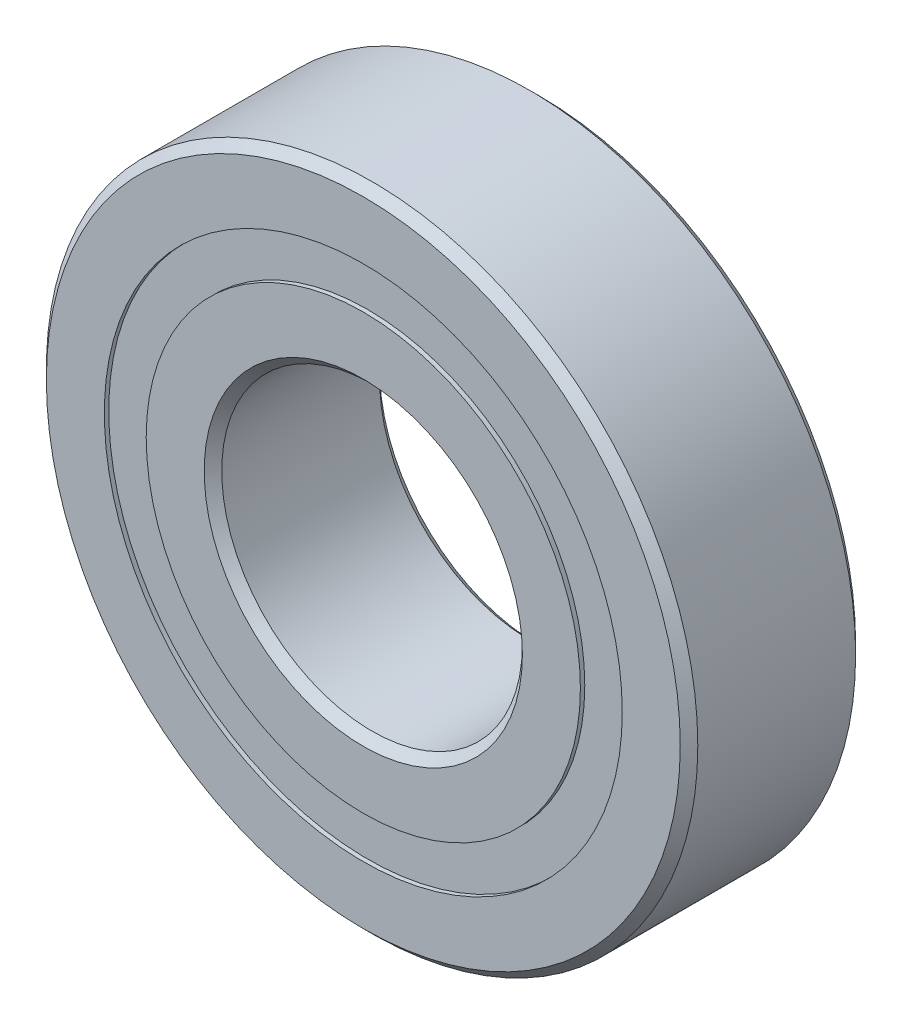
SolidWorks part; units mm, degrees
ref_plane "Front Plane" through (0, 0, 0) normal (0, 0, 1) x (1, 0, 0)
ref_plane "Top Plane" through (0, 0, 0) normal (0, 1, 0) x (1, 0, 0)
ref_plane "Right Plane" through (0, 0, 0) normal (1, 0, 0) x (0, 0, -1)
sketch "Sketch1" plane through (0, 0, 0) normal (1, 0, 0) x (0, 0, -1)
  line L0 (-5.5562, 0) -> (5.5562, 0) construction
  line L1 (0, 20.6375) -> (0, -20.6375) construction
  line L2 (5.0006, 20.6375) -> (-5.0006, 20.6375)
  line L3 (-5.0006, 20.6375) -> (-5.5563, 20.0819)
  line L4 (-5.5563, 20.0819) -> (-5.5563, 16.4071)
  line L5 (-5.5563, 16.4071) -> (-2.4694, 16.4071)
  line L6 (5.5563, 16.4071) -> (2.4694, 16.4071)
  line L7 (5.5563, 20.0819) -> (5.5563, 16.4071)
  line L8 (5.0006, 20.6375) -> (5.5563, 20.0819)
  line L9 (0, 20.6375) -> (0, 15.0813) construction
  line L10 (0, 15.0813) -> (0, 9.525) construction
  arc A0 (-2.4694, 16.4071) -> (2.4694, 16.4071) centre (0, 15.0813) cw
  point P14 (0, 9.525)
  dimension "Width" = 11.1125
  dimension "OD" = 41.275
  dimension "D1" = 45
  dimension "D2" = 0.5556
  dimension "Shaft Dia" = 19.05
  dimension "D3" = 4.9389
  dimension "D4" = 1.3258
revolve "Revolve1" add sketch "Sketch1" angle 360 about L0
sketch "Sketch3" plane through (0, 0, 0) normal (1, 0, 0) x (0, 0, -1)
  line L0 (-5.5563, 13.7554) -> (-2.4694, 13.7554)
  line L1 (0, 20.6375) -> (0, -20.6375) construction
  line L2 (-5.5563, 20.0819) -> (-5.5563, 16.4071) construction
  line L3 (-5.5563, 13.7554) -> (-5.5563, 10.0806)
  line L4 (-5.0006, 20.6375) -> (-5.5563, 20.0819) construction
  line L5 (-5.5563, 10.0806) -> (-5.0006, 9.525)
  line L6 (-5.0006, 9.525) -> (5.0006, 9.525)
  line L7 (5.0006, 20.6375) -> (5.0006, -20.6375) construction
  line L8 (5.0006, 9.525) -> (5.5563, 10.0806)
  line L9 (5.5563, -20.0819) -> (5.5563, 20.0819) construction
  line L10 (5.5563, 10.0806) -> (5.5563, 13.7554)
  line L11 (5.5563, 13.7554) -> (2.4694, 13.7554)
  line L13 (5.0006, 20.6375) -> (5.5563, 20.0819) construction
  arc A0 (2.4694, 16.4071) -> (-2.4694, 16.4071) centre (0, 15.0813) ccw construction
  arc A1 (2.4694, 13.7554) -> (-2.4694, 13.7554) centre (0, 15.0812) cw
revolve "Revolve3" add sketch "Sketch3" angle 360 about L0
sketch "Sketch4" plane through (0, 0, 0) normal (1, 0, 0) x (0, 0, -1)
  line L0 (-2.8028, 15.0813) -> (2.8028, 15.0813)
  arc A2 (-2.8028, 15.0813) -> (2.8028, 15.0813) centre (0, 15.0813) cw
  arc A3 (2.4694, 16.4071) -> (-2.4694, 16.4071) centre (0, 15.0813) ccw construction
revolve "Revolve4" add sketch "Sketch4" angle 360 about L0
ref_axis "Axis1" through (0, 0, -5.5562) along (0, 0, 1)
pattern_circular "CirPattern1" count 12 every 30 about axis through (0, 0, -5.5562) along (0, 0, 1) of bodies 104
sketch "Sketch5" plane through (0, 0, 0) normal (1, 0, 0) x (0, 0, -1)
  line L0 (-5.5563, 16.4071) -> (-2.4694, 16.4071) construction
  line L1 (-5.2784, 16.4071) -> (-2.8028, 16.4071)
  line L2 (-5.2784, 16.4071) -> (-5.2784, 13.7554)
  line L3 (-5.2784, 13.7554) -> (-2.8028, 13.7554)
  line L4 (-2.8028, 16.4071) -> (-2.8028, 13.7554)
  line L5 (-5.5563, 13.7554) -> (-2.4694, 13.7554) construction
  line L6 (5.5563, 16.4071) -> (2.4694, 16.4071) construction
  line L7 (5.2784, 16.4071) -> (2.8028, 16.4071)
  line L8 (5.2784, 16.4071) -> (5.2784, 13.7554)
  line L9 (5.2784, 13.7554) -> (2.8028, 13.7554)
  line L10 (2.8028, 16.4071) -> (2.8028, 13.7554)
  line L11 (5.5563, 13.7554) -> (2.4694, 13.7554) construction
  line L12 (-5.0006, 20.6375) -> (-5.5563, 20.0819) construction
  point P18 (-5.2784, 20.3597)
revolve "Revolve5" add sketch "Sketch5" angle 360 about L0
equation "\"D2@Sketch1\" = \"Width@Sketch1\"*.05"
equation "\"D3@Sketch1\" = \"Width@Sketch1\"/2.25"
equation "\"D4@Sketch1\" = (((\"OD@Sketch1\"-\"Width@Sketch1\")/2)/3.25)/3.5"
equation "\"D2@CirPattern1\" = 360/\"Balls@CirPattern1\""
